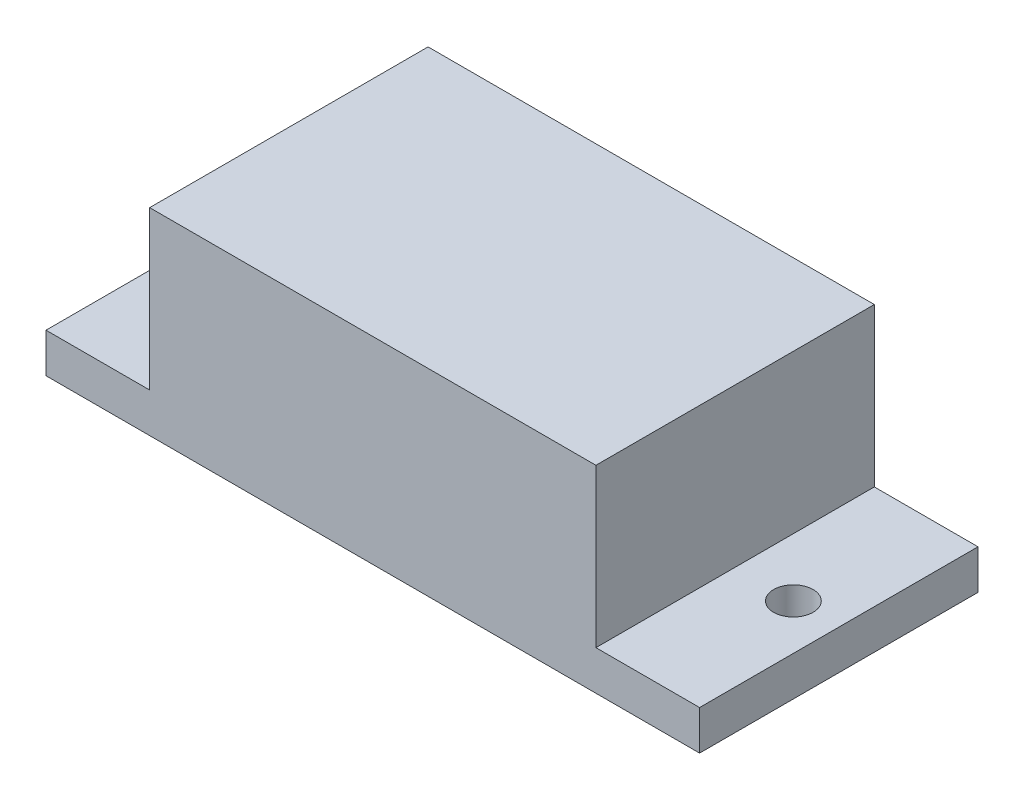
SolidWorks part; units mm, degrees
ref_plane "Front Plane" through (0, 0, 0) normal (0, 0, 1) x (1, 0, 0)
ref_plane "Top Plane" through (0, 0, 0) normal (0, 1, 0) x (1, 0, 0)
ref_plane "Right Plane" through (0, 0, 0) normal (1, 0, 0) x (0, 0, -1)
sketch "Sketch1" plane through (0, 0, 0) normal (0, 1, 0) x (1, 0, 0)
  line L1 (-11.3, -7.05) -> (11.3, -7.05)
  line L2 (-11.3, -7.05) -> (-11.3, 7.05)
  line L3 (-11.3, 7.05) -> (11.3, 7.05)
  line L4 (11.3, -7.05) -> (11.3, 7.05)
  line L5 (-11.3, -7.05) -> (11.3, 7.05) construction
  line L6 (-11.3, 7.05) -> (11.3, -7.05) construction
  point P0 (0, 0)
  dimension "D1" = 14.1
  dimension "D2" = 22.6
extrude "Boss-Extrude1" add sketch "Sketch1" along normal blind 8
sketch "Sketch2" plane through (0, 0, 0) normal (0, -1, 0) x (1, 0, 0)
  line L0 (-11.3, 7.05) -> (11.3, 7.05) construction
  line L1 (-16.55, -7.05) -> (16.55, -7.05)
  line L2 (-16.55, -7.05) -> (-16.55, 7.05)
  line L3 (-16.55, 7.05) -> (16.55, 7.05)
  line L4 (16.55, -7.05) -> (16.55, 7.05)
  line L5 (-16.55, -7.05) -> (16.55, 7.05) construction
  line L6 (-16.55, 7.05) -> (16.55, -7.05) construction
  point P0 (0, 0)
  dimension "D1" = 33.1
extrude "Boss-Extrude2" add sketch "Sketch2" along normal blind 2
hole_wizard "Ø2.0 (2) Diameter Hole1" positions "Sketch3" profile "Sketch4" hole size "Ø2.0" standard "ISO" end condition up to next
sketch "Sketch3" plane through (0, 0, 0) normal (0, 1, 0) x (1, 0, 0)
  line L0 (-14.25, 0) -> (14.25, 0) construction
  point P9 (-14.25, 0)
  point P11 (14.25, 0)
  point P20 (0, 0)
  dimension "D1" = 28.5
sketch "Sketch4" plane through (-14.25, 0, 0) normal (1, 0, 0) x (0, 0, 1)
  line L0 (0, 0) -> (0, 2)
  line L1 (0, 2) -> (1, 2)
  line L2 (1, 2) -> (1, 0)
  line L5 (1, 0) -> (0, 0)
  line L11 (0, -6.35) -> (0, 107.95) construction
  dimension "Thru Hole Dia." = 2
  dimension "Thru Hole Depth" = 2
